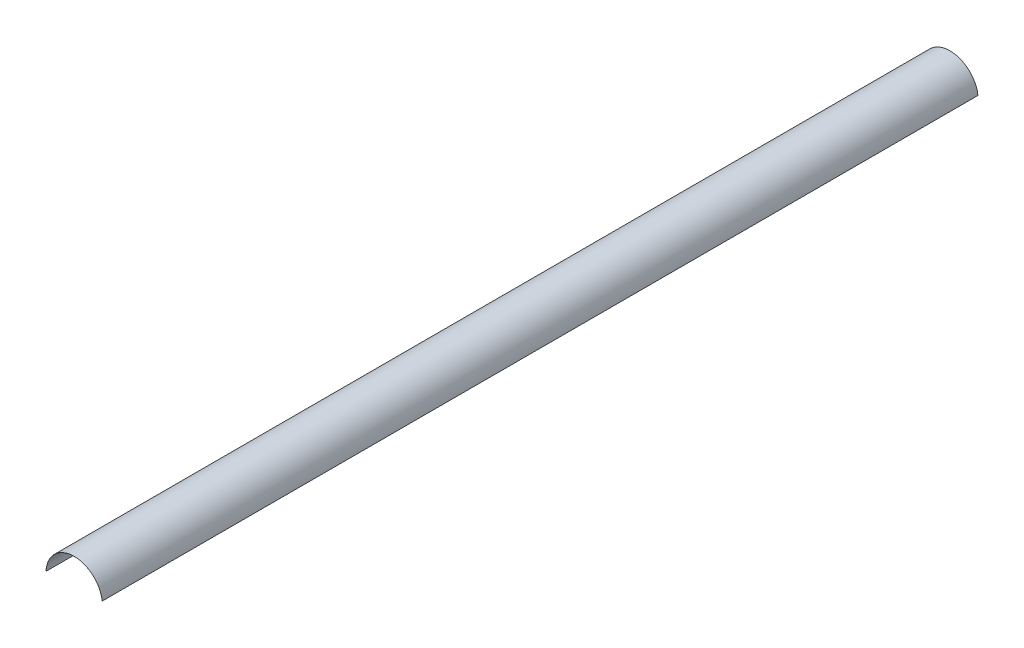
SolidWorks part; units mm, degrees
ref_plane "Front Plane" through (0, 0, 0) normal (0, 0, 1) x (1, 0, 0)
ref_plane "Top Plane" through (0, 0, 0) normal (0, 1, 0) x (1, 0, 0)
ref_plane "Right Plane" through (0, 0, 0) normal (1, 0, 0) x (0, 0, -1)
sketch "Sketch1" plane through (0, 0, 0) normal (0, 0, 1) x (1, 0, 0)
  arc A0 (0, 0) -> (207.2116, 8.6895) centre (103.9716, -4.3791) cw
extrude "Extrude-Thin1" add sketch "Sketch1" along normal blind 3225.8 thin thin type one direction wall 0.127
